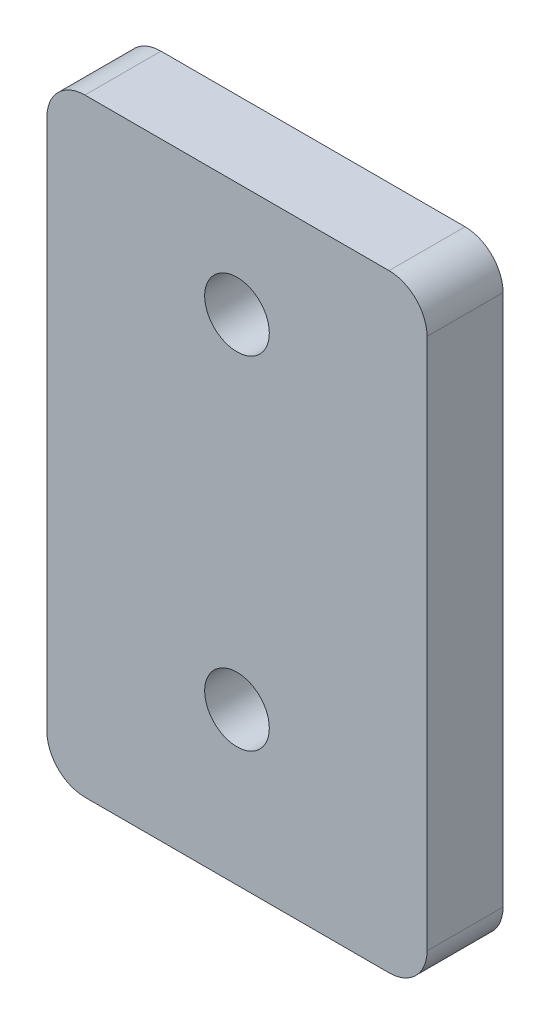
SolidWorks part; units mm, degrees
note: The reader was unsure of these and kept them because the rebuilt part matched: thickness of "Taban-Flanş1", "Sac-Levha1", "Sac-Levha2".
material "1.4003 (X2CrNi12)"
ref_plane "Ön Düzlem" through (0, 0, 0) normal (0, 0, 1) x (1, 0, 0)
ref_plane "Üst Düzlem" through (0, 0, 0) normal (0, 1, 0) x (1, 0, 0)
ref_plane "Sağ Düzlem" through (0, 0, 0) normal (1, 0, 0) x (0, 0, -1)
sketch "Çizim1" plane through (0, 0, 0) normal (0, 0, 1) x (1, 0, 0)
  line L1 (-25, 40) -> (25, 40)
  line L2 (-25, 40) -> (-25, -40)
  line L3 (-25, -40) -> (25, -40)
  line L4 (25, 40) -> (25, -40)
  line L5 (-25, 40) -> (25, -40) construction
  line L6 (-25, -40) -> (25, 40) construction
  point P0 (0, 0)
  dimension "D1" = 80
  dimension "D2" = 50
base flange "Taban-Flanş1" sketch "Çizim1" thickness 10 reverse thickness direction no parameters "D1"=5
sketch "Çizim6" plane through (0, 0, 0) normal (0, 0, 1) x (1, 0, 0)
  circle A4 centre (0, 25) radius 4.25
  circle A5 centre (0, -20) radius 4.25
  dimension "D1" = 8.5
  dimension "D3" = 20
  dimension "D2" = 25
extrude "Kes-Ekstrüzyon1" cut sketch "Çizim6" against normal blind 20
cosmetic thread "Kozmetik Diş Açma1"
cosmetic thread "Kozmetik Diş Açma2"
fillet "Radyus1" radius 5 4 edges at (25, -40, -5) (-25, -40, -5) (-25, 40, -5) (25, 40, -5)
sketch "Büküm-Çizgileri1" [suppressed] plane through (0, 0, 0) normal (0, 1, 0) x (1, 0, 0)
sketch "Sınırlandırma-Kutusu1" [suppressed] plane through (0, 0, 0) normal (0, 1, 0) x (1, 0, 0)
sheet metal parameters "Sac-Levha1" thickness 10 parameters "D1"=5
flat pattern "Düz-Çoğaltma1" [suppressed]
sketch "Büküm-Çizgileri2" plane through (0, 0, 0) normal (0, 1, 0) x (1, 0, 0)
sketch3d "Sınırlandırma-Kutusu2" [suppressed]
  line L0 (-20, 70, 0) -> (-20, -70, 0) construction
  line L1 (20, 70, 0) -> (20, -70, 0) construction
  line L2 (-20, 70, 0) -> (20, 70, 0) construction
  line L3 (-20, -70, 0) -> (20, -70, 0) construction
sheet metal parameters "Sac-Levha2" thickness 10 parameters "D1"=5, "D7"=5
flat pattern "Düz-Çoğaltma1"
sketch "Büküm-Çizgileri2" plane through (0, 0, 0) normal (0, 1, 0) x (1, 0, 0)
sketch3d "Sınırlandırma-Kutusu2" [suppressed]
  line L0 (25, -40, 0) -> (25, 40, 0) construction
  line L1 (-25, -40, 0) -> (-25, 40, 0) construction
  line L2 (25, -40, 0) -> (-25, -40, 0) construction
  line L3 (25, 40, 0) -> (-25, 40, 0) construction
